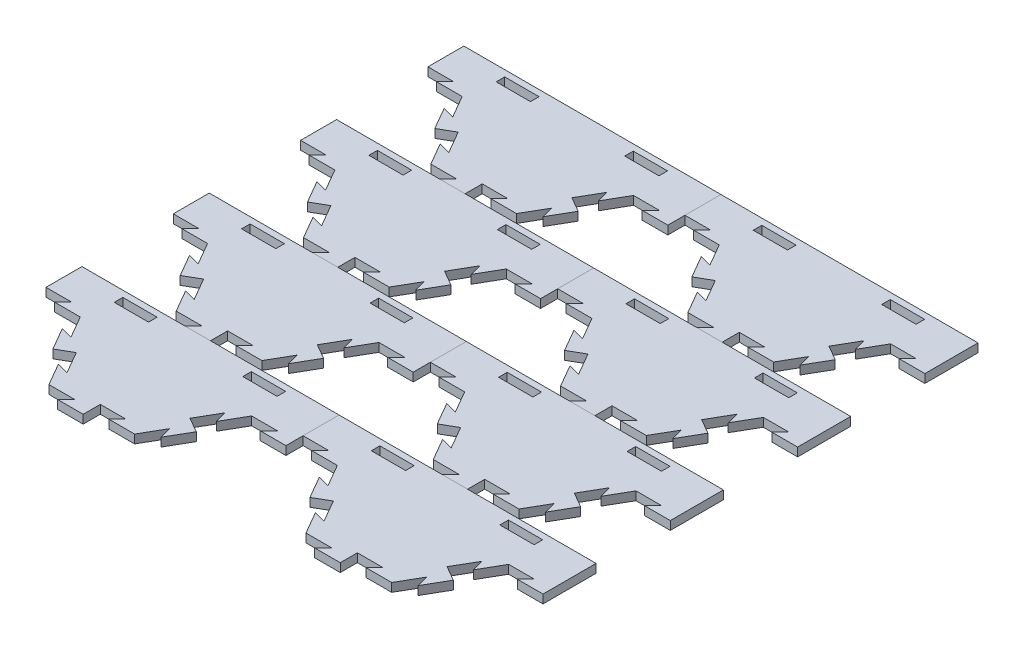
SolidWorks part; units mm, degrees
material "Cedar"
ref_plane "Front Plane" through (0, 0, 0) normal (0, 0, 1) x (1, 0, 0)
ref_plane "Top Plane" through (0, 0, 0) normal (0, 1, 0) x (1, 0, 0)
ref_plane "Right Plane" through (0, 0, 0) normal (1, 0, 0) x (0, 0, -1)
sketch "Sketch1" plane through (0, 0, 0) normal (0, 1, 0) x (1, 0, 0)
  line L0 (0, 0) -> (63.5, 0) construction
  line L1 (63.5, 0) -> (31.75, 54.9926)
  line L2 (31.75, 54.9926) -> (-31.75, 54.9926)
  line L3 (-31.75, 54.9926) -> (-63.5, 0)
  line L4 (-63.5, 0) -> (-31.75, -54.9926)
  line L5 (-31.75, -54.9926) -> (31.75, -54.9926)
  line L6 (31.75, -54.9926) -> (63.5, 0)
  circle A0 centre (0, 0) radius 54.9926 construction
  dimension "D1" = 63.5
extrude "Boss-Extrude1" add sketch "Sketch1" against normal blind 6.35
sketch "Sketch2" plane through (0, 0, 0) normal (0, 1, 0) x (1, 0, 0)
  point P1 (0, 0)
ref_axis "Axis1" through (0, 0, 0) along (0, 1, 0)
sketch "Sketch10" plane through (0, 0, 0) normal (0, 1, 0) x (1, 0, 0)
  line L0 (31.75, 54.9926) -> (41.275, 38.4948) construction
  line L1 (41.275, 38.4948) -> (32.6007, 40.8191)
  line L2 (32.6007, 40.8191) -> (42.1257, 24.3213)
  line L3 (42.1257, 24.3213) -> (47.625, 27.4963)
  line L4 (41.275, 38.4948) -> (47.625, 27.4963)
  line L5 (63.5, 0) -> (31.75, 54.9926) construction
  dimension "D1" = 45
  dimension "D2" = 6.35
extrude "Cut-Extrude4" cut sketch "Sketch10" against normal through all
sketch "Sketch11" plane through (0, 0, 0) normal (0, 1, 0) x (1, 0, 0)
  line L0 (47.625, 27.4963) -> (63.5, 0) construction
  line L1 (47.625, 27.4963) -> (53.1243, 30.6713)
  line L2 (53.1243, 30.6713) -> (62.6493, 14.1735)
  line L3 (62.6493, 14.1735) -> (53.975, 16.4978)
  line L4 (53.975, 16.4978) -> (47.625, 27.4963)
  line L5 (53.975, 16.4978) -> (63.5, 0) construction
  line L6 (53.975, 16.4978) -> (63.5, 0) construction
  line L7 (63.5, 0) -> (47.625, 27.4963) construction
  line L8 (31.75, -54.9926) -> (63.5, 0) construction
  dimension "D1" = 45
  dimension "D2" = 6.35
extrude "Boss-Extrude4" add sketch "Sketch11" against normal blind 6.35
pattern_circular "CirPattern7" count 6 over 360 about axis through (0, 0, 0) along (0, 1, 0) of "Cut-Extrude4", "Boss-Extrude4"
sketch "Sketch12" plane through (0, 0, 0) normal (0, 1, 0) x (1, 0, 0)
  line L0 (-63.5, 0) -> (63.5, 0)
  line L1 (63.5, 0) -> (63.5, 61.3426)
  line L2 (63.5, 61.3426) -> (-63.5, 61.3426)
  line L3 (-63.5, 61.3426) -> (-63.5, 0)
extrude "Cut-Extrude5" cut sketch "Sketch12" against normal through all
sketch "Sketch13" plane through (0, 0, 0) normal (0, 0, -1) x (-1, 0, 0)
  line L0 (0, -6.35) -> (0, 0) construction
  line L1 (95.25, -6.35) -> (-95.25, -6.35)
  line L2 (95.25, -6.35) -> (95.25, 0)
  line L3 (95.25, 0) -> (-95.25, 0)
  line L4 (-95.25, -6.35) -> (-95.25, 0)
  line L5 (63.5, -6.35) -> (-63.5, -6.35) construction
  dimension "D1" = 190.5
extrude "Boss-Extrude5" add sketch "Sketch13" along normal blind 32.9956
sketch "Sketch15" plane through (0, 0, 0) normal (0, 1, 0) x (1, 0, 0)
  line L0 (-63.5, 0) -> (-82.55, 0) construction
  line L1 (-82.55, 0) -> (-76.2, 6.35)
  line L2 (-76.2, 6.35) -> (-95.25, 6.35)
  line L3 (-95.25, 6.35) -> (-95.25, 0)
  line L4 (-82.55, 0) -> (-95.25, 0)
  line L6 (-95.25, 0) -> (-63.5, 0) construction
  line L7 (-95.25, 32.9956) -> (-95.25, 0) construction
  dimension "D1" = 45
  dimension "D2" = 6.35
extrude "Cut-Extrude6" cut sketch "Sketch15" against normal through all
sketch "Sketch16" plane through (0, 0, 0) normal (0, 1, 0) x (1, 0, 0)
  line L0 (63.5, 0) -> (82.55, 0) construction
  line L1 (82.55, 0) -> (76.2, -6.35)
  line L2 (76.2, -6.35) -> (95.25, -6.35)
  line L3 (95.25, -6.35) -> (95.25, 0)
  line L4 (82.55, 0) -> (95.25, 0)
  dimension "D1" = 45
  dimension "D2" = 6.35
extrude "Boss-Extrude6" add sketch "Sketch16" against normal up to surface (6.35 mm away) up to face at (-5.6696, -6.35, 24.6859)
sketch "Sketch17" plane through (0, 0, 0) normal (0, 1, 0) x (1, 0, 0)
  line L0 (0, 32.9956) -> (0, 17.3485) construction
  line L1 (-47.625, 25.172) -> (47.625, 25.172) construction
  line L2 (-60.325, 28.347) -> (-34.925, 28.347)
  line L3 (-60.325, 28.347) -> (-60.325, 21.997)
  line L4 (-60.325, 21.997) -> (-34.925, 21.997)
  line L5 (-34.925, 28.347) -> (-34.925, 21.997)
  line L6 (-60.325, 28.347) -> (-34.925, 21.997) construction
  line L7 (-60.325, 21.997) -> (-34.925, 28.347) construction
  line L8 (34.925, 28.347) -> (60.325, 28.347)
  line L9 (34.925, 28.347) -> (34.925, 21.997)
  line L10 (34.925, 21.997) -> (60.325, 21.997)
  line L11 (60.325, 28.347) -> (60.325, 21.997)
  line L12 (34.925, 28.347) -> (60.325, 21.997) construction
  line L13 (34.925, 21.997) -> (60.325, 28.347) construction
  line L14 (-95.25, 32.9956) -> (95.25, 32.9956) construction
  line L15 (-95.25, 17.3485) -> (95.25, 17.3485) construction
  line L16 (-95.25, 32.9956) -> (-95.25, 6.35) construction
  line L17 (95.25, 32.9956) -> (95.25, -6.35) construction
  point P4 (0, 25.172)
  point P5 (0, 25.172)
  dimension "D1" = 6.35
  dimension "D2" = 25.4
  dimension "D3" = 6.35
  dimension "D4" = 25.4
  dimension "D5" = 95.25
  dimension "D6" = 15.6471
extrude "Cut-Extrude8" cut sketch "Sketch17" against normal through all
pattern_linear "LPattern1" count 2 spacing 190.5 along (1, 0, 0) of bodies 135
pattern_linear "LPattern2" count 4 spacing 94.3382 along (0, 0, 1) of bodies 136 135
